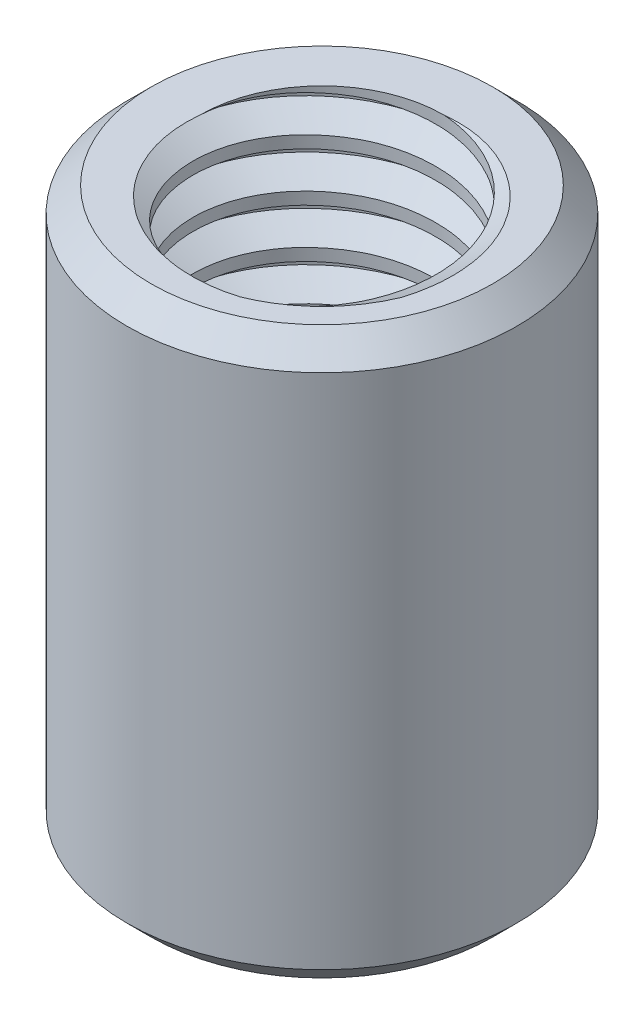
SolidWorks part; units mm, degrees
ref_plane "Front Plane" through (0, 0, 0) normal (0, 0, 1) x (1, 0, 0)
ref_plane "Top Plane" through (0, 0, 0) normal (0, 1, 0) x (1, 0, 0)
ref_plane "Right Plane" through (0, 0, 0) normal (1, 0, 0) x (0, 0, -1)
sketch "Sketch1" plane through (0, 0, 0) normal (0, 1, 0) x (1, 0, 0)
  circle A0 centre (0, 0) radius 2
  dimension "D1" = 4
extrude "Boss-Extrude1" add sketch "Sketch1" along normal blind 5.8
sketch "Sketch2" plane through (0, 5.8, 0) normal (0, 1, 0) x (1, 0, 0)
  point P0 (0, 0)
hole_wizard "Tap Drill for M3 Tap1" positions "Sketch3" profile "Sketch4" hole size "M3" standard "ISO" end condition through all
sketch "Sketch3" plane through (0, 5.8, 0) normal (0, 1, 0) x (1, 0, 0)
  point P0 (0, 0)
sketch "Sketch4" plane through (0, 5.8, 0) normal (1, 0, 0) x (0, 0, 1)
  line L0 (0, 0) -> (0, 5.8)
  line L1 (0, 5.8) -> (1.25, 5.8)
  line L2 (1.25, 5.8) -> (1.25, 0)
  line L5 (1.25, 0) -> (0, 0)
  line L11 (0, -6.35) -> (0, 107.95) construction
  dimension "Thru Hole Dia." = 2.5
  dimension "Thru Hole Depth" = 5.8
thread "Thread1" pitch 0.5 method cut profile "Thread Profile1" start angle 0, offset 1, length 10, pitch 0.5, diameter 2.5
ref_plane "Plane1" through (-1.25, 6.8, 0) normal (0, 0, 1) x (-1, 0, 0)
sketch "Thread Profile1" plane through (-1.25, 6.8, 0) normal (0, 0, 1) x (-1, 0, 0)
  line L0 (0, 0) -> (0, 0.5) construction
  line L1 (0, 0) -> (0.2706, 0.1562)
  line L2 (0.2706, 0.1562) -> (0.2706, 0.2187)
  line L3 (0.2706, 0.2187) -> (0, 0.375)
  line L4 (0.2706, 0.1875) -> (0, 0.1875) construction
  line L11 (0, 0) -> (0, 0.375)
  point P2 (0, 0)
  dimension "Pitch" = 0.5
  dimension "Profile_Angle" = 60
  dimension "Profile_Land" = 0.0625
  dimension "Profile_Height" = 0.2706
chamfer "Chamfer1" distance 0.25 angle 45 2 edges at (0, 5.8, 2) (0, 0, 2)
